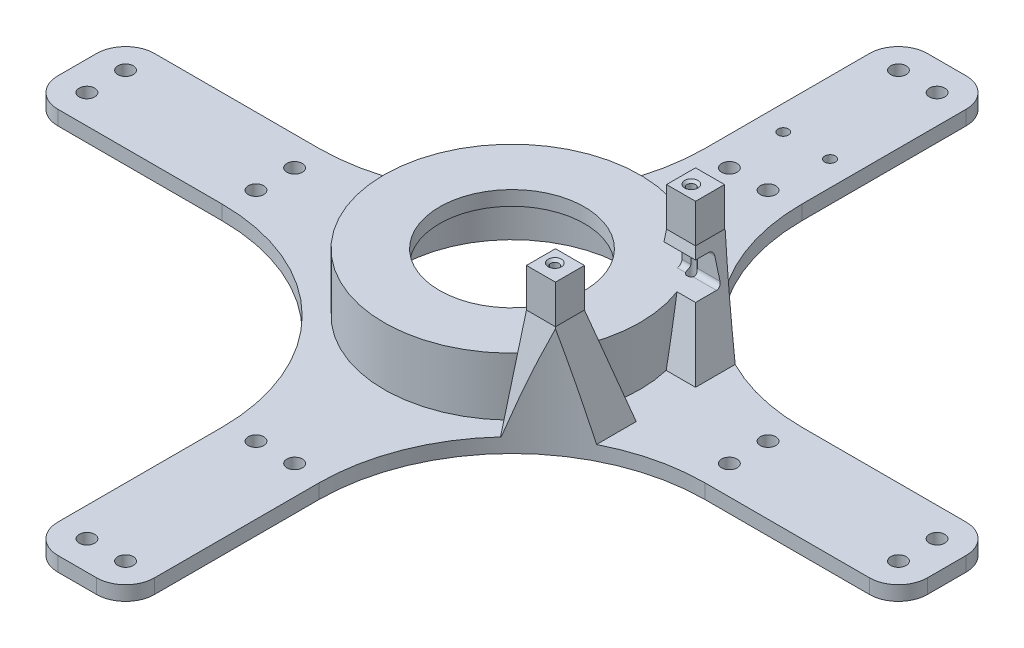
SolidWorks part; units mm, degrees
material "PLA"
ref_plane "Front Plane" through (0, 0, 0) normal (0, 0, 1) x (1, 0, 0)
ref_plane "Top Plane" through (0, 0, 0) normal (0, 1, 0) x (1, 0, 0)
ref_plane "Right Plane" through (0, 0, 0) normal (1, 0, 0) x (0, 0, -1)
sketch "Sketch1" plane through (0, 0, 0) normal (0, 1, 0) x (1, 0, 0)
  line L0 (0, 90) -> (0, -90) construction
  line L1 (-90, 0) -> (90, 0) construction
  line L2 (50, 10) -> (84, 10)
  line L3 (4, 90) -> (-4, 90)
  line L4 (10, 84) -> (10, 50)
  line L5 (4, -90) -> (-4, -90)
  line L6 (-10, 84) -> (-10, 50)
  line L7 (-84, 10) -> (-50, 10)
  line L8 (-90, 4) -> (-90, -4)
  line L9 (-84, -10) -> (-50, -10)
  line L10 (90, 4) -> (90, -4)
  line L11 (10, -50) -> (10, -84)
  line L12 (50, -10) -> (84, -10)
  line L13 (-10, -50) -> (-10, -84)
  arc A0 (4, 90) -> (10, 84) centre (4, 84) cw
  arc A1 (-4, 90) -> (-10, 84) centre (-4, 84) ccw
  arc A2 (84, 10) -> (90, 4) centre (84, 4) cw
  arc A3 (84, -10) -> (90, -4) centre (84, -4) ccw
  arc A4 (10, -84) -> (4, -90) centre (4, -84) cw
  arc A5 (-4, -90) -> (-10, -84) centre (-4, -84) cw
  arc A6 (-90, -4) -> (-84, -10) centre (-84, -4) ccw
  arc A7 (-84, 10) -> (-90, 4) centre (-84, 4) ccw
  arc A8 (50, 10) -> (10, 50) centre (50, 50) cw
  arc A9 (10, -50) -> (50, -10) centre (50, -50) cw
  arc A10 (-50, -10) -> (-10, -50) centre (-50, -50) cw
  arc A11 (-10, 50) -> (-50, 10) centre (-50, 50) cw
  point P5 (0, 0)
  point P8 (0, 0)
  point P16 (0, 90)
  point P23 (10, 90)
  point P26 (-10, 90)
  point P43 (10, -10)
  point P46 (-10, -10)
  dimension "D1" = 20
  dimension "D3" = 6
  dimension "D4" = 40
  dimension "D2" = 180
extrude "Boss-Extrude1" add sketch "Sketch1" along normal mid plane 3
hole_wizard "M3 Clearance Hole1" positions "Sketch3" profile "Sketch4" hole size "M3" standard "ANSI Metric" end condition up to next
sketch "Sketch3" plane through (0, 1.5, 0) normal (0, 1, 0) x (1, 0, 0)
  line L0 (-49, 4) -> (-49, -4) construction
  line L2 (-49, 4) -> (-84, 4) construction
  line L3 (-84, 4) -> (-84, -4) construction
  line L4 (-84, -4) -> (-49, -4) construction
  line L6 (-4, -49) -> (-4, -84) construction
  line L7 (-4, -84) -> (4, -84) construction
  line L8 (4, -84) -> (4, -49) construction
  line L9 (4, -49) -> (-4, -49) construction
  line L11 (49, -4) -> (84, -4) construction
  line L12 (84, -4) -> (84, 4) construction
  line L13 (84, 4) -> (49, 4) construction
  line L14 (49, 4) -> (49, -4) construction
  line L16 (4, 49) -> (4, 84) construction
  line L17 (4, 84) -> (-4, 84) construction
  line L18 (-4, 84) -> (-4, 49) construction
  line L19 (-4, 49) -> (4, 49) construction
  point P0 (-84, 4)
  point P3 (-84, -4)
  point P6 (-4, 84)
  point P9 (4, 84)
  point P12 (84, 4)
  point P15 (84, -4)
  point P18 (4, -84)
  point P21 (-4, -84)
  point P24 (-49, 4)
  point P26 (-49, -4)
  point P28 (-4, 49)
  point P30 (4, 49)
  point P32 (49, 4)
  point P34 (49, -4)
  point P36 (-4, -49)
  point P38 (4, -49)
  dimension "D1" = 35
sketch "Sketch4" plane through (-84, 1.5, -4) normal (1, 0, 0) x (0, 0, 1)
  line L0 (0, 0) -> (0, 3)
  line L1 (0, 3) -> (1.6, 3)
  line L2 (1.6, 3) -> (1.6, 0)
  line L5 (1.6, 0) -> (0, 0)
  line L11 (0, -6.35) -> (0, 107.95) construction
  dimension "Thru Hole Dia." = 3.2
  dimension "Thru Hole Depth" = 3
sketch "Sketch5" plane through (0, 1.5, 0) normal (0, 1, 0) x (1, 0, 0)
  circle A0 centre (0, 0) radius 23.5
  dimension "D1" = 47
extrude "Cut-Extrude1" cut sketch "Sketch5" against normal through all both and the other way through all
sketch "Sketch6" plane through (0, 1.5, 0) normal (0, 1, 0) x (1, 0, 0)
  circle A0 centre (0, 0) radius 23.5 construction
  circle A1 centre (0, 0) radius 23.5
  circle A2 centre (0, 0) radius 26.5
  dimension "D1" = 3
extrude "Boss-Extrude2" add sketch "Sketch6" along normal blind 9
sketch "Sketch7" plane through (0, 10.5, 0) normal (0, 1, 0) x (1, 0, 0)
  circle A0 centre (0, 0) radius 15
  circle A1 centre (0, 0) radius 26.5
  circle A2 centre (0, 0) radius 26.5
  dimension "D2" = 30
  dimension "D1" = 0
extrude "Boss-Extrude3" add sketch "Sketch7" along normal blind 3
sketch "Sketch8" plane through (0, 13.5, 0) normal (0, -1, 0) x (1, 0, 0)
  line L9 (20.4939, 17.5) -> (26.4939, 17.5)
  line L10 (20.4939, 17.5) -> (20.4939, 11.5)
  line L11 (20.4939, 11.5) -> (26.4939, 11.5)
  line L12 (26.4939, 17.5) -> (26.4939, 11.5)
  line L13 (20.4939, -17.5) -> (26.4939, -17.5)
  line L14 (20.4939, -17.5) -> (20.4939, -11.5)
  line L15 (20.4939, -11.5) -> (26.4939, -11.5)
  line L16 (26.4939, -17.5) -> (26.4939, -11.5)
  circle A6 centre (0, 0) radius 23.5 construction
  dimension "D3" = 6
  dimension "D1" = 23
  dimension "D2" = 6
extrude "Boss-Extrude4" add sketch "Sketch8" along normal up to next and the other way blind 16
hole_wizard "Tap Drill for M2.2x0.45 Tap2" positions "Sketch11" profile "Sketch12" hole size "M2.2x0.45" standard "ANSI Metric" end condition up to next
sketch "Sketch11" plane through (0, 29.5, 0) normal (0, 1, 0) x (1, 0, 0)
  line L0 (22.9939, 14.125) -> (22.9939, -14.125) construction
  line L5 (20.4939, 11.5) -> (20.4939, 17.5) construction
  point P0 (22.9939, 14.125)
  point P2 (22.9939, -14.125)
  point P10 (22.9939, 0)
  dimension "D1" = 28.25
  dimension "D2" = 2.5
sketch "Sketch12" plane through (22.9939, 29.5, -14.125) normal (1, 0, 0) x (0, 0, 1)
  line L0 (0, 0) -> (0, 31)
  line L1 (0, 31) -> (0.875, 31)
  line L2 (0.875, 31) -> (0.875, 0)
  line L5 (0.875, 0) -> (0, 0)
  line L11 (0, -6.35) -> (0, 107.95) construction
  dimension "Thru Hole Dia." = 1.75
  dimension "Thru Hole Depth" = 31
chamfer "Chamfer1" distance 20 angle 15 6 edges at (23.4939, 1.5, 17.5) (26.4939, 1.5, 14.5) (23.4939, 1.5, -17.5) (26.4939, 1.5, -14.5) (25.1843, 1.5, 11.5) (25.1843, 1.5, -11.5) first distance on face at (23.4939, 15.5, 17.5) first distance on face at (26.4939, 15.5, 14.5) first distance on face at (23.4939, 15.5, -17.5) first distance on face at (26.4939, 15.5, -14.5) first distance on face at (23.6208, 14.8333, 11.5) first distance on face at (23.6208, 14.8333, -11.5)
sketch "Sketch13" plane through (26.4939, 0, 0) normal (1, 0, 0) x (0, 0, -1)
  line L0 (9.3564, 13.5) -> (-9.3564, 13.5) construction
  line L1 (14.6888, 19.5) -> (4.6417, 19.5)
  line L2 (14.6888, 19.5) -> (14.6888, 13.5)
  line L3 (14.6888, 13.5) -> (4.6417, 13.5)
  line L4 (4.6417, 19.5) -> (4.6417, 13.5)
  dimension "D1" = 6
extrude "Cut-Extrude2" cut sketch "Sketch13" against normal mid plane 20
fillet "Fillet2" radius 1 4 edges at (21.4093, 19.5, -14.6888) (25.3464, 19.5, -14.6888) (21.4093, 13.5, -14.6888) (26.1503, 13.5, -14.6888)
hole_wizard "M2 Clearance Hole1" positions "Sketch15" profile "Sketch16" hole size "M2" standard "ANSI Metric" end condition up to next
sketch "Sketch15" plane through (0, 1.5, 0) normal (0, 1, 0) x (1, 0, 0)
  line L0 (-4.845, 61) -> (4.845, 61) construction
  line L5 (0, 61) -> (0, 0) construction
  point P0 (-4.845, 61)
  point P2 (4.845, 61)
  dimension "D1" = 61
  dimension "D2" = 9.69
sketch "Sketch16" plane through (-4.845, 1.5, -61) normal (1, 0, 0) x (0, 0, 1)
  line L0 (0, 0) -> (0, 3)
  line L1 (0, 3) -> (1.1, 3)
  line L2 (1.1, 3) -> (1.1, 0)
  line L5 (1.1, 0) -> (0, 0)
  line L11 (0, -6.35) -> (0, 107.95) construction
  dimension "Thru Hole Dia." = 2.2
  dimension "Thru Hole Depth" = 3
chamfer "Chamfer2" distance 0.5 angle 45 2 edges at (22.9939, 29.5, 15) (22.9939, 29.5, -13.25)
